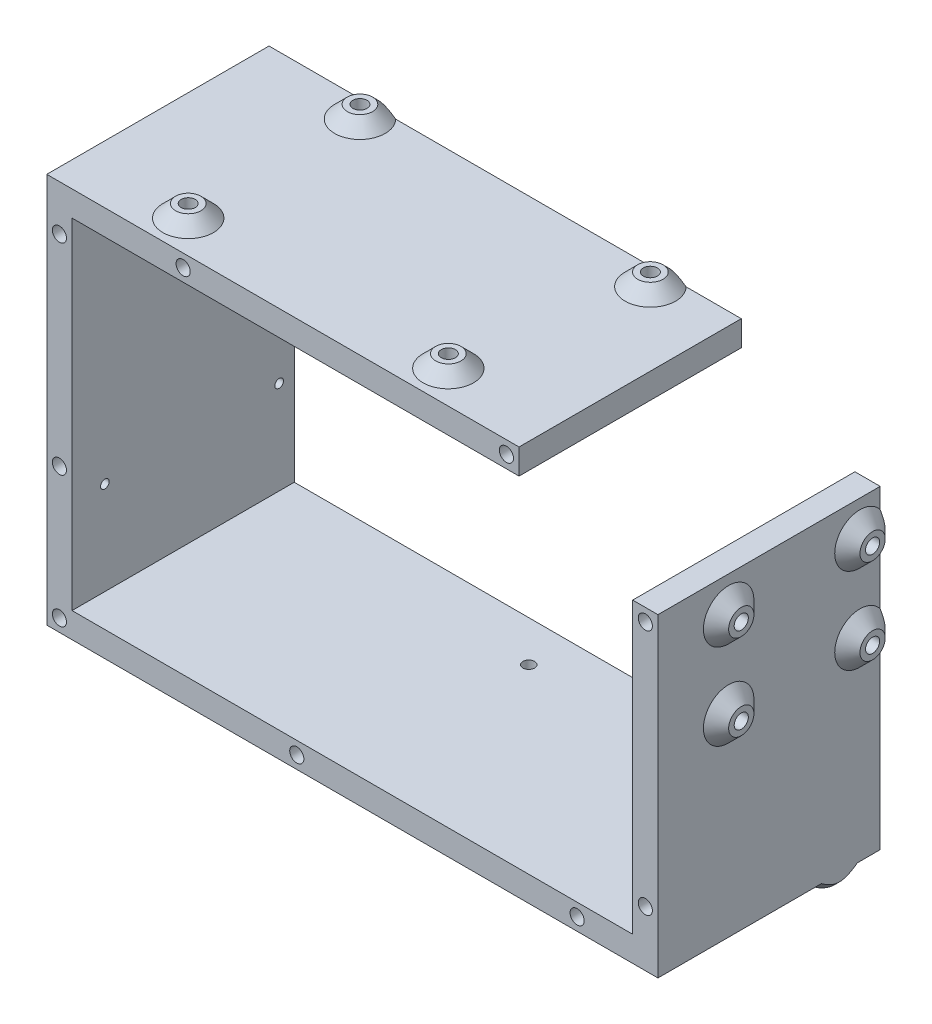
SolidWorks part; units mm, degrees
material "Nylon 101 60%"
ref_plane "Front Plane" through (0, 0, 0) normal (0, 0, 1) x (1, 0, 0)
ref_plane "Top Plane" through (0, 0, 0) normal (0, 1, 0) x (1, 0, 0)
ref_plane "Right Plane" through (0, 0, 0) normal (1, 0, 0) x (0, 0, -1)
sketch "Sketch1" plane through (0, 0, 0) normal (0, 0, 1) x (1, 0, 0)
  line L1 (-60.5, 38.65) -> (60.5, 38.65)
  line L2 (-60.5, 38.65) -> (-60.5, -38.65)
  line L3 (-60.5, -38.65) -> (60.5, -38.65)
  line L4 (60.5, 38.65) -> (60.5, -38.65)
  line L5 (-60.5, 38.65) -> (60.5, -38.65) construction
  line L6 (-60.5, -38.65) -> (60.5, 38.65) construction
  point P0 (0, 0)
  dimension "D1" = 121
  dimension "D2" = 77.3
extrude "Box" add sketch "Sketch1" along normal blind 44
sketch "Sketch2" plane through (0, 0, 0) normal (0, 0, 1) x (1, 0, 0)
  line L0 (55.5, -33.65) -> (60.5, -33.65) construction
  line L1 (-55.5, 33.65) -> (55.5, 33.65)
  line L2 (-55.5, 33.65) -> (-55.5, -33.65)
  line L3 (-55.5, -33.65) -> (55.5, -33.65)
  line L4 (55.5, 33.65) -> (55.5, -33.65)
  line L5 (-55.5, 33.65) -> (55.5, -33.65) construction
  line L6 (-55.5, -33.65) -> (55.5, 33.65) construction
  line L7 (60.5, -38.65) -> (60.5, 38.65) construction
  line L8 (55.5, -33.65) -> (55.5, -38.65) construction
  line L9 (-60.5, -38.65) -> (60.5, -38.65) construction
  point P0 (0, 0)
  dimension "D1" = 5
extrude "Cutout" cut sketch "Sketch2" along normal up to next
sketch "Sketch3" plane through (0, 0, 0) normal (0, 0, 1) x (1, 0, 0)
  line L0 (33, 38.65) -> (33, 33.65)
  line L1 (60.5, 38.65) -> (-60.5, 38.65) construction
  line L2 (55.5, 33.65) -> (-55.5, 33.65) construction
  line L3 (33, 33.65) -> (55.5, 23.65)
  line L4 (55.5, 23.65) -> (60.5, 23.65)
  line L5 (60.5, -38.65) -> (60.5, 38.65) construction
  line L6 (60.5, 23.65) -> (60.5, 38.65)
  line L7 (60.5, 38.65) -> (33, 38.65)
  line L8 (55.5, -33.65) -> (55.5, 33.65) construction
  dimension "D1" = 22.5
  dimension "D2" = 10
extrude "Trim" cut sketch "Sketch3" along normal up to next
sketch "Sketch4" plane through (0, 0, 44) normal (0, 0, 1) x (1, 0, 0)
  line L0 (55.5, -33.65) -> (55.5, -38.65) construction
  line L1 (-60.5, -38.65) -> (60.5, -38.65) construction
  line L2 (58, 21.15) -> (58, 23.65) construction
  line L3 (55.5, 23.65) -> (60.5, 23.65) construction
  line L4 (-58, -36.15) -> (-11, -36.15) construction
  line L5 (-60.5, 38.65) -> (-60.5, -38.65) construction
  line L6 (-58, -33.65) -> (-58, -38.65) construction
  line L7 (55.5, -36.15) -> (-11, -36.15) construction
  line L9 (30.5, 36.15) -> (33, 36.15) construction
  line L11 (33, 38.65) -> (33, 33.65) construction
  line L12 (-33.5, 36.15) -> (-60.5, 36.15) construction
  line L20 (-55.5, -33.65) -> (-60.5, -33.65) construction
  line L21 (-58, -33.65) -> (-58, 29.65) construction
  line L24 (-33.5, 36.15) -> (30.5, 36.15) construction
  line L28 (58, 21.15) -> (58, -27.65) construction
  circle A0 centre (-58, -36.15) radius 1.4
  circle A1 centre (58, -27.65) radius 1.4
  circle A3 centre (-11, -36.15) radius 1.4
  circle A5 centre (-58, 29.65) radius 1.4
  circle A6 centre (-33.5, 36.15) radius 1.4
  circle A8 centre (30.5, 36.15) radius 1.4
  circle A9 centre (58, 21.15) radius 1.4
  circle A10 centre (44.5, -36.15) radius 1.4
  circle A11 centre (-58, -10.15) radius 1.4
  point P41 (-58, -33.65)
  dimension "D1" = 2.8
  dimension "D2" = 27
  dimension "D3" = 11
  dimension "D4" = 11
  dimension "D5" = 47
  dimension "D6" = 6.5
  dimension "D7" = 2.5
  dimension "D8" = 23.5
extrude "Top screws" cut sketch "Sketch4" against normal blind 9.5
sketch "Sketch7" plane through (-60.5, 0, 0) normal (-1, 0, 0) x (0, 0, 1)
  circle A0 centre (3, -15.2) radius 1.1 construction
  circle A1 centre (37.5, -15.2) radius 1.1 construction
  circle A2 centre (3, 32.8) radius 1.1 construction
  circle A3 centre (37.5, 32.8) radius 1.1 construction
  circle A4 centre (3, -15.2) radius 1.1 construction
  circle A5 centre (37.5, -15.2) radius 1.1 construction
  circle A6 centre (3, 32.8) radius 1.1 construction
  circle A7 centre (37.5, 32.8) radius 1.1 construction
  circle A8 centre (3, 32.8) radius 2.5
  circle A9 centre (37.5, 32.8) radius 2.5
  circle A10 centre (3, -15.2) radius 2.5
  circle A11 centre (37.5, -15.2) radius 2.5
  dimension "D1" = 5
extrude "USB power boss" add sketch "Sketch7" along normal up to surface (2.5 mm away)
chamfer "Chamfer2" distance 2.5 angle 45 4 edges at (-60.5, -12.7, 3) (-60.5, -12.7, 37.5) (-60.5, 35.3, 37.5) (-60.5, 35.3, 3)
sketch "Sketch8" plane through (-55.5, 0, 0) normal (1, 0, 0) x (0, 0, -1)
  circle A0 centre (-3, -15.2) radius 0.85
  circle A1 centre (-37.5, -15.2) radius 0.85
  circle A2 centre (-3, 32.8) radius 0.85
  circle A3 centre (-37.5, 32.8) radius 0.85
  dimension "D1" = 1.7
extrude "USB power screws" cut sketch "Sketch8" against normal up to next
sketch "Sketch9" plane through (0, 38.65, 0) normal (0, 1, 0) x (1, 0, 0)
  circle A0 centre (12.5, -37.5) radius 1.7 construction
  circle A1 centre (-39, -37.5) radius 1.7 construction
  circle A2 centre (-39, -3.5) radius 1.7 construction
  circle A3 centre (18.5, -3.5) radius 1.7 construction
  circle A4 centre (12.5, -37.5) radius 1.7 construction
  circle A5 centre (-39, -37.5) radius 1.7 construction
  circle A6 centre (-39, -3.5) radius 1.7 construction
  circle A7 centre (18.5, -3.5) radius 1.7 construction
  circle A8 centre (-39, -37.5) radius 2.5
  circle A9 centre (-39, -3.5) radius 2.5
  circle A10 centre (18.5, -3.5) radius 2.5
  circle A11 centre (12.5, -37.5) radius 2.5
  dimension "D1" = 5
extrude "Motor drivers boss" add sketch "Sketch9" along normal up to surface (2.5 mm away)
chamfer "Chamfer3" distance 2.5 angle 45 4 edges at (-39, 38.65, 35) (-39, 38.65, 1) (18.5, 38.65, 1) (12.5, 38.65, 35)
sketch "Sketch11" plane through (0, 33.65, 0) normal (0, -1, 0) x (1, 0, 0)
  circle A0 centre (12.5, 37.5) radius 1.4
  circle A1 centre (18.5, 3.5) radius 1.4
  circle A2 centre (-39, 3.5) radius 1.4
  circle A3 centre (-39, 37.5) radius 1.4
  dimension "D1" = 2.8
extrude "Motor drivers screws" cut sketch "Sketch11" against normal up to next
sketch "Sketch12" plane through (0, -38.65, 0) normal (0, -1, 0) x (1, 0, 0)
  circle A0 centre (-1, 8.0765) radius 1.35 construction
  circle A1 centre (-1, 8.0765) radius 1.35 construction
  circle A2 centre (57, 8.0765) radius 1.35 construction
  circle A3 centre (57, 8.0765) radius 1.35 construction
  circle A4 centre (-1, 8.0765) radius 2.5
  circle A5 centre (57, 8.0765) radius 2.5
  dimension "D1" = 5
extrude "Boss-Extrude5" add sketch "Sketch12" along normal blind 2.5
sketch "Sketch13" plane through (0, -33.65, 0) normal (0, -1, 0) x (1, 0, 0)
  circle A0 centre (-1, 8.0765) radius 1.15
  circle A1 centre (57, 8.0765) radius 1.15
  dimension "D1" = 2.3
extrude "Cut-Extrude8" cut sketch "Sketch13" along normal up to next
chamfer "Chamfer4" distance 2.5 angle 45 2 edges at (57, -38.65, 10.5765) (-1, -38.65, 10.5765)
sketch "Sketch14" plane through (0, 0, 0) normal (0, 0, 1) x (1, 0, 0)
  line L0 (-1, -0.65) -> (71.2163, -42.3441) construction
  line L1 (-1, -0.65) -> (71.2163, -42.3441) construction
  line L2 (-73.2163, -42.3441) -> (-1, -0.65) construction
  line L3 (-73.2163, -42.3441) -> (-1, -0.65) construction
  line L4 (-1, -0.65) -> (-1, 82.7382) construction
  line L5 (-1, -0.65) -> (-1, 82.7382) construction
  line L6 (0, -33.65) -> (0, -38.65) construction
  line L7 (-55.5, -33.65) -> (55.5, -33.65) construction
  line L8 (-60.5, -38.65) -> (60.5, -38.65) construction
  line L9 (-55.5, 0) -> (-60.5, 0) construction
  line L10 (-55.5, 33.65) -> (-55.5, -33.65) construction
  line L11 (-60.5, 28.8) -> (-60.5, -11.2) construction
  line L12 (-11.25, 33.65) -> (-11.25, 38.65) construction
  line L13 (33, 33.65) -> (-55.5, 33.65) construction
  line L14 (14.9293, 38.65) -> (-35.4293, 38.65) construction
  line L15 (60.5, -7.5) -> (55.5, -7.5) construction
  line L16 (60.5, -38.65) -> (60.5, 23.65) construction
  line L17 (55.5, -33.65) -> (55.5, 23.65) construction
  line L18 (0, -36.15) -> (-60.5, -36.15) construction
  line L19 (-60.5, -19.2) -> (-60.5, -38.65) construction
  line L20 (0, -36.15) -> (60.5, -36.15) construction
  line L21 (58, -7.5) -> (58, 23.65) construction
  line L22 (55.5, 23.65) -> (60.5, 23.65) construction
  line L23 (58, -7.5) -> (58, -36.15) construction
  line L24 (-58, 0) -> (-58, -36.15) construction
  line L25 (-58, 0) -> (-58, 38.65) construction
  line L26 (-42.5707, 38.65) -> (-60.5, 38.65) construction
  line L27 (-11.25, 36.15) -> (-58, 36.15) construction
  line L28 (-11.25, 36.15) -> (33, 36.15) construction
  line L29 (33, 38.65) -> (33, 33.65) construction
  circle A0 centre (53, -36.15) radius 1.4
  circle A1 centre (58, -29.15) radius 1.4
  circle A2 centre (58, 20.65) radius 1.4
  circle A3 centre (30, 36.15) radius 1.4
  circle A4 centre (2, 36.15) radius 1.4
  circle A5 centre (-4, 36.15) radius 1.4
  circle A6 centre (-48, 36.15) radius 1.4
  circle A7 centre (-58, 26.15) radius 1.4
  circle A8 centre (-58, -30.15) radius 1.4
  circle A9 centre (-53, -36.15) radius 1.4
  circle A10 centre (-7, -36.15) radius 1.4
  dimension "D1" = 2.8
  dimension "D2" = 3
  dimension "D3" = 3
  dimension "D4" = 3
  dimension "D5" = 7
  dimension "D6" = 5
  dimension "D7" = 3
  dimension "D8" = 7
  dimension "D9" = 5
  dimension "D10" = 6
  dimension "D11" = 10
  dimension "D12" = 10
extrude "Chassis screws" cut sketch "Sketch14" along normal blind 10
sketch "Sketch15" plane through (60.5, 0, 0) normal (1, 0, 0) x (0, 0, -1)
  line L0 (0, -38.65) -> (0, 23.65) construction
  line L1 (0, -3.35) -> (0, 2.65)
  line L2 (0, 13.65) -> (0, 19.65)
  circle A0 centre (-30, -0.35) radius 1.6 construction
  circle A1 centre (-30, 16.65) radius 1.6 construction
  circle A2 centre (-4, 16.65) radius 1.6 construction
  circle A3 centre (-4, -0.35) radius 1.6 construction
  circle A4 centre (-30, -0.35) radius 1.6 construction
  circle A5 centre (-30, 16.65) radius 1.6 construction
  circle A6 centre (-4, 16.65) radius 1.6 construction
  circle A7 centre (-4, -0.35) radius 1.6 construction
  circle A8 centre (-30, -0.35) radius 5
  circle A9 centre (-30, 16.65) radius 5
  arc A10 (0, 2.65) -> (0, -3.35) centre (-4, -0.35) ccw
  arc A11 (0, 19.65) -> (0, 13.65) centre (-4, 16.65) ccw
  dimension "D1" = 10
extrude "LDS adapter board" add sketch "Sketch15" along normal up to surface (2.5 mm away)
sketch "Sketch16" plane through (63, 0, 0) normal (1, 0, 0) x (0, 0, -1)
  circle A0 centre (-30, -0.35) radius 1.4
  circle A1 centre (-30, 16.65) radius 1.4
  circle A2 centre (-4, 16.65) radius 1.4
  circle A3 centre (-4, -0.35) radius 1.4
  dimension "D1" = 2.8
extrude "Cut-Extrude10" cut sketch "Sketch16" against normal up to next
chamfer "Chamfer5" distance 2.5 angle 45 4 edges at (63, -0.35, 9) (63, 16.65, 9) (63, 21.65, 30) (63, 4.65, 30)
